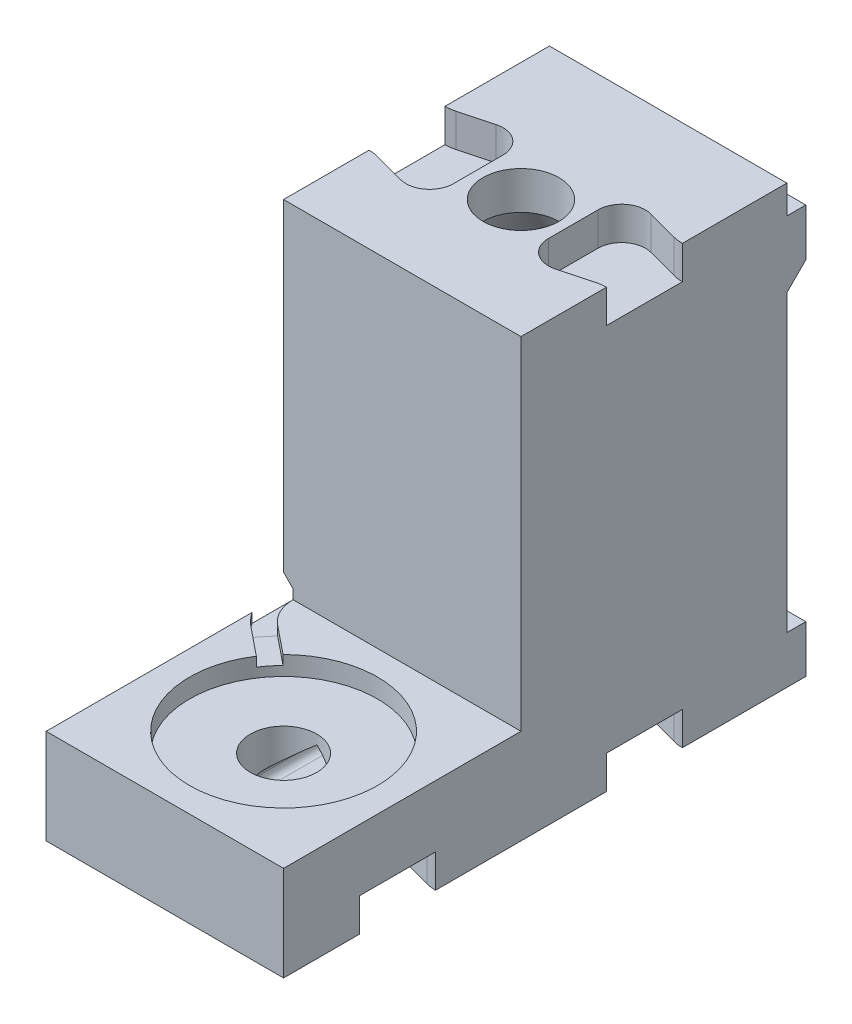
SolidWorks part; units mm, degrees
ref_plane "Płaszczyzna przednia" through (0, 0, 0) normal (0, 0, 1) x (1, 0, 0)
ref_plane "Płaszczyzna górna" through (0, 0, 0) normal (0, 1, 0) x (1, 0, 0)
ref_plane "Płaszczyzna prawa" through (0, 0, 0) normal (1, 0, 0) x (0, 0, -1)
sketch "Sketch1" plane through (0, 0, 0) normal (0, 1, 0) x (1, 0, 0)
  line L0 (0, -12.5) -> (0, 12.5) construction
  circle A0 centre (0, -12.5) radius 9.9
  circle A1 centre (0, 12.5) radius 10
  point P8 (0, 0)
  dimension "D1" = 19.8
  dimension "D2" = 20
  dimension "D3" = 25
sketch "Sketch2" plane through (0, 0, 0) normal (0, 1, 0) x (1, 0, 0)
  line L0 (0, 1.5) -> (0, 0) construction
  line L1 (-12.5, -25) -> (12.5, -25)
  line L2 (-12.5, -25) -> (-12.5, 28)
  line L3 (-12.5, 28) -> (12.5, 28)
  line L4 (12.5, -25) -> (12.5, 28)
  line L5 (-12.5, -25) -> (12.5, 28) construction
  line L6 (-12.5, 28) -> (12.5, -25) construction
  point P0 (0, 1.5)
  dimension "D1" = 25
  dimension "D2" = 25
  dimension "D3" = 28
extrude "Boss-Extrude1" add sketch "Sketch2" against normal blind 10
sketch "Sketch4" plane through (0, 0, 0) normal (0, 1, 0) x (1, 0, 0)
  circle A0 centre (0, -12.5) radius 9.9 construction
  circle A1 centre (0, -12.5) radius 9.9
extrude "Cut-Extrude3" cut sketch "Sketch4" against normal blind 2
sketch "Sketch5" plane through (0, -2, 0) normal (0, 1, 0) x (1, 0, 0)
  circle A0 centre (0, -12.5) radius 3.5
  dimension "D1" = 7
extrude "Cut-Extrude4" cut sketch "Sketch5" against normal blind 5
sketch "Sketch6" plane through (0, 0, 0) normal (0, 0, 1) x (1, 0, 0)
  line L0 (3.5, -7) -> (-3.5, -7) construction
  line L1 (3.5, -7) -> (-3.5, -7)
  line L2 (3.5, -2) -> (-3.5, -2) construction
  line L3 (3.5, -2) -> (-3.5, -2) construction
  line L6 (0, 0) -> (0, -7) construction
  line L7 (0, -3) -> (3.5, -5.9368)
  line L8 (3.5, -5.9368) -> (3.5, -7)
  line L9 (0, -3) -> (-3.5, -5.9368)
  line L10 (-3.5, -5.9368) -> (-3.5, -7)
  dimension "D1" = 50
  dimension "D2" = 1
extrude "Cut-Extrude6" cut sketch "Sketch6" along normal up to vertex (12.5 mm away) and the other way up to vertex (12.5 mm away) contours L9 L10 L1 L8 L7 region at (0, -5.5923, 0) up to point (0, 0, 12.5) other way up to point (0, 0, -12.5)
ref_axis "Axis3" through (0, -8.2471, -12.5) along (0, 1, 0)
sketch "Sketch8" plane through (0, 0, 0) normal (1, 0, 0) x (0, 0, -1)
  line L0 (-12.5, -7) -> (-16, -7) construction
  line L1 (-12.5, -7) -> (-16, -7) construction
  line L2 (22.5, 0) -> (2.5, 0) construction
  line L3 (22.5, 0) -> (2.5, 0) construction
  line L4 (-9, -2) -> (-16, -2) construction
  line L5 (-9, -2) -> (-16, -2) construction
  line L6 (9, -2) -> (16, -2) construction
  line L8 (12.5, 0) -> (12.5, -7)
  line L9 (12.5, -8.2471) -> (12.5, 3.3354) construction
  line L10 (12.5, -7) -> (16, -7)
  line L11 (16, -7) -> (16, -2)
  line L12 (16, -2) -> (22.5, 0)
  line L13 (22.5, 0) -> (12.5, 0)
  point P9 (12.5, -2)
revolve "Cut-Revolve1" cut sketch "Sketch8" angle 360 about axis through (0, -8.2471, -12.5) along (0, 1, 0)
fillet "Fillet1" radius 0.75 4 edges at (-3.5, -7, 0) (0, -7, -16) (3.5, -7, 0) (0, -7, 16)
fillet "Fillet2" radius 0.75 2 edges at (3.5, -5.9368, 0) (-3.5, -5.9368, 0)
sketch "Sketch9" plane through (0, 0, 0) normal (0, 1, 0) x (1, 0, 0)
  line L0 (-12.5, 28) -> (-12.5, -25) construction
  line L1 (-12.5, 0) -> (12.5, 0)
  line L2 (-12.5, 0) -> (-12.5, 28)
  line L3 (-12.5, 28) -> (12.5, 28)
  line L4 (12.5, 0) -> (12.5, 28)
extrude "Boss-Extrude2" add sketch "Sketch9" along normal blind 36
sketch "Sketch10" plane through (0, 0, 0) normal (1, 0, 0) x (0, 0, -1)
  line L0 (0, 36) -> (28, 36) construction
  line L1 (0, 36) -> (28, 36) construction
  line L2 (2.5, 0) -> (22.5, 0) construction
  line L3 (2.5, 0) -> (22.5, 0) construction
  line L4 (12.5, 0) -> (12.5, 36)
  line L6 (16.5, 32) -> (22.5, 21.6077)
  line L7 (22.5, 21.6077) -> (22.5, 0)
  line L8 (22.5, 0) -> (12.5, 0)
  line L9 (16.5, 32) -> (16.5, 36)
  line L10 (16.5, 36) -> (12.5, 36)
  dimension "D1" = 4
  dimension "D2" = 30
  dimension "D3" = 4
revolve "Cut-Revolve2" cut sketch "Sketch10" angle 360 about axis through (0, -8.2471, -12.5) along (0, 1, 0)
fillet "Fillet3" radius 0.75 1 edges at (0, -2, -16)
fillet "Fillet4" radius 2 2 edges at (0, 0, -22.5) (0, 21.6077, -22.5)
sketch "Sketch11" plane through (0, 0, 0) normal (0, 1, 0) x (1, 0, 0)
  line L0 (-12.5, 28) -> (-12.5, 0)
  line L1 (-12.5, 0) -> (12.5, 0) construction
  line L2 (-10.645, -3.887) -> (0, -12.5)
  arc A0 (-12.5, 0) -> (-10.645, -3.887) centre (-7.5, 0) ccw
  dimension "D1" = 5
sketch "Sketch12" plane through (0, 0, -28) normal (0, 0, -1) x (-1, 0, 0)
  line L0 (12.5, 0) -> (-12.5, 0) construction
  line L1 (12.5, 0) -> (-12.5, 0) construction
  line L3 (13.5, -1) -> (11.5, -1)
  line L12 (13.5, -1) -> (13.5, 1)
  line L13 (13.5, 1) -> (11.5, 1)
  line L14 (11.5, -1) -> (11.5, 1)
  line L15 (13.5, -1) -> (11.5, 1) construction
  line L16 (13.5, 1) -> (11.5, -1) construction
  dimension "D1" = 2
  dimension "D2" = 2
sweep "Cut-Sweep1" cut profiles "Sketch12" path "Sketch11"
sketch "Sketch14" plane through (0, 0, -28) normal (0, 0, -1) x (-1, 0, 0)
  line L0 (0, 0) -> (0, 13) construction
  line L1 (-10.1, -7) -> (-2.15, -7)
  line L2 (-10.1, -7) -> (-10.1, 20.85)
  line L3 (-10.1, 33) -> (10.1, 33)
  line L4 (10.1, -7) -> (10.1, 20.85)
  line L5 (-10.1, -7) -> (10.1, 33) construction
  line L6 (-10.1, 33) -> (10.1, -7) construction
  line L7 (-10.1, 25.15) -> (-10.1, 33)
  line L8 (10.1, 25.15) -> (10.1, 33)
  line L9 (2.15, -7) -> (10.1, -7)
  line L10 (0, 0) -> (0, -7) construction
  line L11 (-2.15, -7) -> (2.15, -7) construction
  arc A0 (10.1, 20.85) -> (10.1, 25.15) centre (10.1, 23) ccw
  arc A1 (-10.1, 25.15) -> (-10.1, 20.85) centre (-10.1, 23) ccw
  arc A2 (-2.15, -7) -> (2.15, -7) centre (0, -7) ccw
  point P0 (0, 13)
  dimension "D4" = 4.3
  dimension "D1" = 20.2
  dimension "D2" = 40
  dimension "D3" = 7
  dimension "D5" = 10
extrude "Cut-Extrude7" cut sketch "Sketch14" against normal blind 2
chamfer "Chamfer1" distance 1 angle 45 1 edges at (-12.5, 1, -14)
sketch "Sketch17" plane through (0, 0, -26) normal (0, 0, -1) x (-1, 0, 0)
  line L0 (0, 0.0857) -> (0, 10.581) construction
  line L1 (-10.1, -7) -> (-2.15, -7) construction
  line L2 (-2, -3.5) -> (2, -3.5)
  line L3 (-2, -3.5) -> (-2, -1.5)
  line L4 (-2, -1.5) -> (2, -1.5)
  line L5 (2, -3.5) -> (2, -1.5)
  line L6 (-2, -3.5) -> (2, -1.5) construction
  line L7 (-2, -1.5) -> (2, -3.5) construction
  line L8 (-4, 28.5) -> (4, 28.5)
  line L9 (-4, 28.5) -> (-4, 30.5)
  line L10 (-4, 30.5) -> (4, 30.5)
  line L11 (4, 28.5) -> (4, 30.5)
  line L12 (-4, 28.5) -> (4, 30.5) construction
  line L13 (-4, 30.5) -> (4, 28.5) construction
  line L14 (10.1, 33) -> (-10.1, 33) construction
  point P1 (0, -2.5)
  point P8 (0, 29.5)
  dimension "D1" = 8
  dimension "D2" = 2
  dimension "D3" = 4
  dimension "D4" = 2
  dimension "D5" = 4.5
  dimension "D6" = 3.5
extrude "Cut-Extrude9" cut sketch "Sketch17" against normal blind 2
chamfer "Chamfer2" distance 2 angle 45 3 edges at (0, -1.5, -26) (0, 30.5, -26) (0, 33, -28)
sketch "Sketch18" plane through (0, -10, 0) normal (0, -1, 0) x (1, 0, 0)
  line L0 (-12.5, -28) -> (-12.5, 25) construction
  line L1 (-11.4647, 8.8637) -> (-8.147, 7.9747)
  line L2 (-5, 15.6105) -> (-5, 10.3895)
  line L3 (-13.8886, 13) -> (-4.9613, 13) construction
  line L4 (-12.5, 9) -> (-12.5, 17)
  line L5 (-11.4647, 17.1363) -> (-8.147, 18.0253)
  line L6 (-12.5, 25) -> (12.5, 25) construction
  circle A1 centre (-12.5, 5) radius 4 construction
  circle A2 centre (-7.5, 10.3895) radius 2.5 construction
  arc A4 (-8.147, 7.9747) -> (-5, 10.3895) centre (-7.5, 10.3895) ccw
  arc A5 (-11.4647, 8.8637) -> (-12.5, 9) centre (-12.5, 5) ccw
  arc A6 (-8.147, 18.0253) -> (-5, 15.6105) centre (-7.5, 15.6105) cw
  arc A7 (-11.4647, 17.1363) -> (-12.5, 17) centre (-12.5, 21) cw
  point P15 (-5, 13)
  point P20 (-12.5, 13)
  dimension "D2" = 8
  dimension "D3" = 5
  dimension "D1" = 8
  dimension "D4" = 5
  dimension "D5" = 15
  dimension "D6" = 12
extrude "Cut-Extrude10" cut sketch "Sketch18" against normal blind 3.5
mirror "Mirror1" about plane through (0, 0, 0) normal (0, 0, 1) of "Cut-Extrude10" second plane through (0, 0, 0) second plane normal (1, 0, 0)
ref_plane "Plane1" through (0, 13, 0) normal (0, -1, 0) x (-1, 0, 0)
mirror "Mirror2" about plane through (0, 13, 0) normal (0, -1, 0) of "Mirror1"
sketch "Sketch19" plane through (0, 0, -28) normal (0, 0, -1) x (-1, 0, 0)
  line L0 (-12.5, -10) -> (-12.5, -5)
  line L1 (-12.5, -10) -> (-12.5, 36) construction
  line L2 (-12.5, -5) -> (-5.5, -5)
  line L3 (-5.5, -5) -> (-3.5, -7)
  line L4 (-10.1, -7) -> (-2.15, -7) construction
  line L5 (0, -7) -> (0, -10) construction
  line L7 (-3.5, -7) -> (3.5, -7)
  line L8 (-12.5, -10) -> (12.5, -10)
  line L9 (-12.5, -10) -> (12.5, -10) construction
  line L10 (5.5, -5) -> (3.5, -7)
  line L11 (12.5, -5) -> (5.5, -5)
  line L12 (12.5, -10) -> (12.5, -5)
  point P18 (0, -7)
  point P21 (0, -10)
  dimension "D1" = 2
  dimension "D2" = 3.5
  dimension "D3" = 135
extrude "Boss-Extrude3" add sketch "Sketch19" along normal blind 2
sketch "Sketch20" plane through (12.5, 0, 0) normal (1, 0, 0) x (0, 0, -1)
  line L0 (28, 33) -> (30, 33)
  line L1 (28, -5) -> (28, 36) construction
  line L2 (30, 33) -> (30, 28)
  line L3 (30, 28) -> (28, 26)
  line L4 (28, 26) -> (28, 33)
  line L5 (17, 36) -> (28, 36) construction
  dimension "D1" = 10
  dimension "D2" = 3
  dimension "D3" = 45
  dimension "D4" = 2
extrude "Boss-Extrude4" add sketch "Sketch20" against normal blind 2.4
sketch "Sketch23" plane through (0, 33, 0) normal (0, 1, 0) x (1, 0, 0)
  line L0 (10.1, 30) -> (9.75, 29.3938)
  line L1 (9.75, 29.3938) -> (9.75, 28.2021)
  line L2 (9.75, 28.2021) -> (10.1, 28)
  line L3 (10.1, 30) -> (10.1, 28)
  dimension "D1" = 30
  dimension "D2" = 60
  dimension "D3" = 0.35
extrude "Boss-Extrude5" add sketch "Sketch23" against normal blind 5 contours L0 L1 L2 L3
mirror "Mirror6" about plane through (0, 0, 0) normal (1, 0, 0) of "Boss-Extrude5", "Boss-Extrude4"
chamfer "Chamfer4" distance 0.5 angle 45 2 edges at (-10.1, 28, -29) (10.1, 28, -29)
